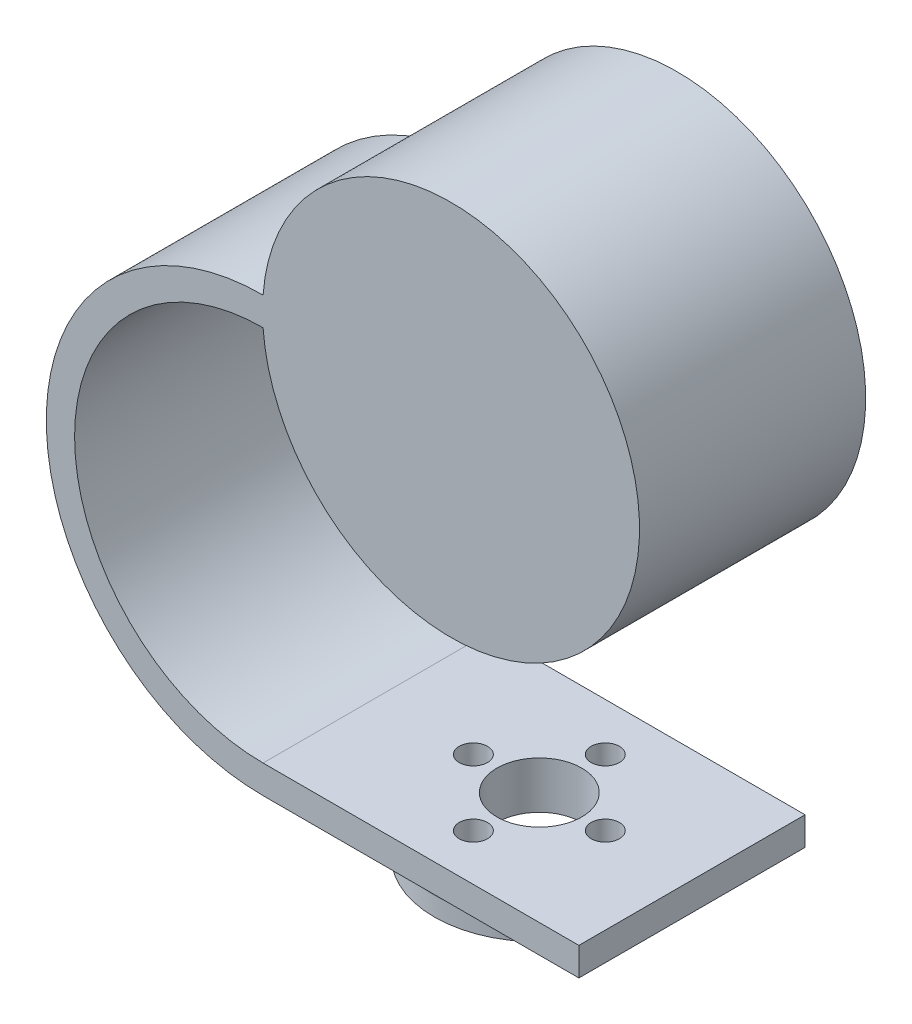
SolidWorks part; units mm, degrees
ref_plane "Front Plane" through (0, 0, 0) normal (0, 0, 1) x (1, 0, 0)
ref_plane "Top Plane" through (0, 0, 0) normal (0, 1, 0) x (1, 0, 0)
ref_plane "Right Plane" through (0, 0, 0) normal (1, 0, 0) x (0, 0, -1)
sketch "Sketch1" plane through (0, 0, 0) normal (0, 0, 1) x (1, 0, 0)
  line L0 (30.2631, -52.2762) -> (30.2631, -49.2762)
  line L5 (30.2631, -49.2762) -> (-3.2473, -49.2762)
  line L6 (30.2631, -52.2762) -> (-3.2473, -52.2762)
  line L8 (-3.2473, -6.2762) -> (-3.2473, -9.2762) construction
  arc A0 (-3.2473, -52.2762) -> (-3.2473, -6.2762) centre (-3.2473, -29.2762) cw
  arc A1 (-3.2473, -49.2762) -> (-3.2473, -9.2762) centre (-3.2473, -29.2762) cw
  arc A2 (-3.2473, -9.2762) -> (-3.2473, -6.2762) centre (16.6963, -7.7762) ccw
  point P8 (16.2372, 2.9544)
  point P9 (-3.2473, -7.7762)
  point P10 (0, 0)
  point P11 (0, 0)
  point P13 (16.6963, -2.7762)
  dimension "D3" = 40
  dimension "D4" = 40
  dimension "D5" = 3
  dimension "D1" = 3
  dimension "D2" = 3
extrude "Boss-Extrude1" add sketch "Sketch1" along normal blind 24
sketch "Sketch2" plane through (0, -52.2762, 0) normal (0, -1, 0) x (1, 0, 0)
  circle A0 centre (14.1199, 12.0545) radius 10
  point P0 (14.1199, 12.0545)
  point P2 (0, 0)
  dimension "D1" = 20
extrude "Boss-Extrude2" add sketch "Sketch2" along normal blind 2
sketch "Sketch3" plane through (0, -54.2762, 0) normal (0, -1, 0) x (1, 0, 0)
  line L0 (14.1199, 2.0545) -> (14.1199, 22.0545) construction
  line L1 (4.1199, 12.0545) -> (24.1199, 12.0545) construction
  circle A0 centre (14.1199, 19.0545) radius 1.5
  circle A1 centre (14.1199, 12.0545) radius 10 construction
  circle A3 centre (21.1199, 12.0545) radius 1.5
  circle A4 centre (14.1199, 5.0545) radius 1.5
  circle A5 centre (7.1199, 12.0545) radius 1.5
  circle A6 centre (14.1199, 12.0545) radius 4.5
  point P10 (14.1199, 12.0545)
  point P20 (14.1199, 12.0545)
  dimension "D1" = 3
  dimension "D4" = 9
  dimension "D2" = 7
  dimension "D5" = 7
  dimension "D3" = 4
extrude "Cut-Extrude1" cut sketch "Sketch3" against normal blind 5
sketch "Sketch6" plane through (0, 0, 0) normal (0, 0, -1) x (-1, 0, 0)
  circle A0 centre (-17.2217, -7.5983) radius 10
  point P2 (-17.2217, -7.5983)
  dimension "D1" = 20
extrude "Boss-Extrude3" add sketch "Sketch6" along normal blind 1
fillet "Fillet2" radius 1 1 edges at (7.2217, -7.5983, 0)
sketch "Sketch7" plane through (0, 0, -1) normal (0, 0, -1) x (-1, 0, 0)
  line L0 (-27.2217, -7.5983) -> (-7.2217, -7.5983) construction
  line L1 (-17.2217, 2.4017) -> (-17.2217, -17.5983) construction
  circle A0 centre (-17.2217, -0.5983) radius 1.5
  circle A1 centre (-17.2217, -7.5983) radius 10 construction
  circle A2 centre (-10.2217, -7.5983) radius 1.5
  circle A3 centre (-17.2217, -14.5983) radius 1.5
  circle A4 centre (-24.2217, -7.5983) radius 1.5
  circle A5 centre (-17.2217, -7.5983) radius 4.5
  point P10 (-17.2217, -7.5983)
  point P18 (-17.2217, -7.5983)
  dimension "D1" = 3
  dimension "D4" = 9
  dimension "D2" = 7
  dimension "D5" = 7
  dimension "D3" = 4
extrude "Cut-Extrude4" cut sketch "Sketch7" against normal blind 10
sketch "Sketch9" plane through (0, -52.2762, 0) normal (0, -1, 0) x (1, 0, 0)
  circle A0 centre (13.9906, 12.0704) radius 11
  circle A3 centre (13.9906, 12.0704) radius 10
  point P2 (13.9383, 11.9538)
  point P3 (13.902, 12.2443)
  point P4 (13.9906, 12.0704)
  point P14 (0, 0)
  dimension "D1" = 22
extrude "Boss-Extrude4" add sketch "Sketch9" along normal blind 3
fillet "Fillet3" radius 1 1 edges at (13.9906, -52.2762, 23.0704)
